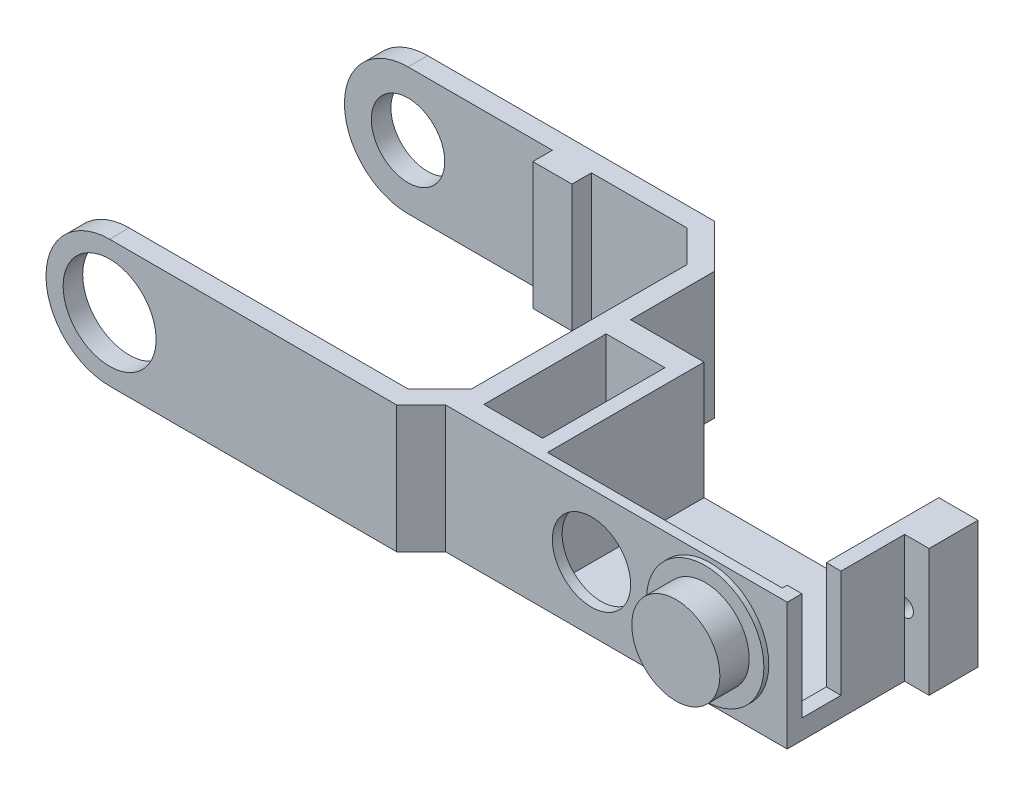
SolidWorks part; units mm, degrees
material "uhlíková ocel 7850"
ref_plane "Přední rovina" through (0, 0, 0) normal (0, 0, 1) x (1, 0, 0)
ref_plane "Horní rovina" through (0, 0, 0) normal (0, 1, 0) x (1, 0, 0)
ref_plane "Pravá rovina" through (0, 0, 0) normal (1, 0, 0) x (0, 0, -1)
sketch "Skica1" plane through (0, 0, 0) normal (0, 1, 0) x (1, 0, 0)
  line L0 (0, -11) -> (0, 11)
  line L1 (0, 11) -> (-3.25, 14.25)
  line L2 (-3.25, 14.25) -> (-38.25, 14.25)
  line L3 (-38.25, 14.25) -> (-38.25, 16.25)
  line L4 (-38.25, 16.25) -> (-2.4216, 16.25)
  line L5 (-2.4216, 16.25) -> (2, 11.8284)
  line L6 (2, 11.8284) -> (2, -11.8284)
  line L7 (2, 0) -> (0, 0) construction
  line L8 (-2.4216, -16.25) -> (2, -11.8284)
  line L9 (-38.25, -16.25) -> (-2.4216, -16.25)
  line L10 (-38.25, -14.25) -> (-38.25, -16.25)
  line L11 (-3.25, -14.25) -> (-38.25, -14.25)
  line L12 (0, -11) -> (-3.25, -14.25)
  dimension "D1" = 11
  dimension "D2" = 135
  dimension "D3" = 35
  dimension "D4" = 2
  dimension "D5" = 2
  dimension "D6" = 2
  dimension "D7" = 14.25
extrude "Přidat vysunutím1" add sketch "Skica1" along normal blind 13
sketch "Skica2" plane through (0, 0, 0) normal (0, -1, 0) x (1, 0, 0)
  line L0 (0.0784, 13.75) -> (35, 13.75)
  line L1 (-2.4216, 16.25) -> (2, 11.8284) construction
  line L2 (35, 13.75) -> (35, 1.75)
  line L3 (35, 1.75) -> (37.5, 1.75)
  line L4 (37.5, 1.75) -> (37.5, -3.25)
  line L5 (37.5, -3.25) -> (2, -3.25)
  line L6 (2, 11.8284) -> (2, -11.8284) construction
  line L7 (2, -3.25) -> (2, 11.8284)
  line L8 (2, 11.8284) -> (0.0784, 13.75)
  line L9 (-38.25, 16.25) -> (-2.4216, 16.25) construction
  line L10 (0, -11) -> (0, 11) construction
  dimension "D1" = 2.5
  dimension "D2" = 35
  dimension "D3" = 12
  dimension "D4" = 5
  dimension "D5" = 2.5
extrude "Přidat vysunutím2" add sketch "Skica2" against normal up to surface (13 mm away) up to face at (-13.3619, 13, 0)
sketch "Skica3" plane through (0, 13, 0) normal (0, 1, 0) x (1, 0, 0)
  line L0 (0, 11) -> (0, -11) construction
  line L1 (2, 0.75) -> (8, 0.75)
  line L2 (2, 0.75) -> (2, -11.75)
  line L3 (2, -11.75) -> (8, -11.75)
  line L4 (8, 0.75) -> (8, -11.75)
  line L5 (37.5, 3.25) -> (2, 3.25) construction
  line L6 (0.0784, -13.75) -> (35, -13.75) construction
  dimension "D1" = 2
  dimension "D2" = 2.5
  dimension "D3" = 2
  dimension "D4" = 6
extrude "Odebrat vysunutím1" cut sketch "Skica3" against normal through all
sketch "Skica4" plane through (0, 13, 0) normal (0, 1, 0) x (1, 0, 0)
  line L0 (37.5, 3.25) -> (2, 3.25) construction
  line L1 (9.5, 3.25) -> (33.5, 3.25)
  line L2 (9.5, 3.25) -> (9.5, -12.75)
  line L3 (9.5, -12.75) -> (33.5, -12.75)
  line L4 (33.5, 3.25) -> (33.5, -12.75)
  line L5 (0.0784, -13.75) -> (35, -13.75) construction
  line L6 (35, -13.75) -> (35, -1.75) construction
  dimension "D1" = 1
  dimension "D2" = 1.5
  dimension "D3" = 24
extrude "Odebrat vysunutím2" cut sketch "Skica4" against normal blind 12
sketch "Skica5" plane through (0, 0, -3.25) normal (0, 0, -1) x (-1, 0, 0)
  circle A0 centre (-34.9938, 6.5551) radius 1.1906 construction
  circle A1 centre (-8.0063, 6.5551) radius 1.1906 construction
  circle A2 centre (-34.9938, 6.5551) radius 0.9
  circle A3 centre (-8.0063, 6.5551) radius 0.9
  dimension "D1" = 1.8
extrude "Odebrat vysunutím3" cut sketch "Skica5" against normal blind 5 contours A1 | A2 | A3 region at (34.9938, 6.5551, -3.25) region at (8.0063, 6.5551, -3.25)
fillet "Zaoblit1" radius 6.5 4 edges at (-38.25, 0, -15.25) (-38.25, 0, 15.25) (-38.25, 13, 15.25) (-38.25, 13, -15.25)
sketch "Skica6" plane through (0, 0, -16.25) normal (0, 0, -1) x (-1, 0, 0)
  circle A0 centre (31.75, 6.5) radius 3.75
  dimension "D1" = 7.5
extrude "Odebrat vysunutím4" cut sketch "Skica6" against normal blind 5
sketch "Skica7" plane through (0, 0, 14.25) normal (0, 0, -1) x (-1, 0, 0)
  circle A0 centre (31.75, 6.5) radius 4.75
  dimension "D1" = 9.5
extrude "Odebrat vysunutím5" cut sketch "Skica7" against normal blind 5
sketch "Skica8" plane through (35, 0, 0) normal (1, 0, 0) x (0, 0, -1)
  line L0 (-13.75, 13) -> (-1.75, 13) construction
  line L1 (-12.25, 13) -> (-8.25, 13)
  line L2 (-12.25, 13) -> (-12.25, 2)
  line L3 (-12.25, 2) -> (-8.25, 2)
  line L4 (-8.25, 13) -> (-8.25, 2)
  line L5 (-13.75, 13) -> (-13.75, 0) construction
  dimension "D1" = 1.5
  dimension "D2" = 4
  dimension "D3" = 11
extrude "Odebrat vysunutím6" cut sketch "Skica8" against normal blind 5
sketch "Skica9" plane through (0, 0, 13.75) normal (0, 0, 1) x (1, 0, 0)
  line L0 (-22.25, 6.555) -> (27.1188, 6.555) construction
  line L3 (35, 13) -> (35, 0) construction
  circle A0 centre (15, 6.555) radius 4
  dimension "D1" = 8
  dimension "D2" = 20
extrude "Odebrat vysunutím7" cut sketch "Skica9" against normal blind 10
sketch "Skica10" plane through (0, 0, 13.75) normal (0, 0, 1) x (1, 0, 0)
  circle A0 centre (27.1188, 6.555) radius 6
  dimension "D1" = 12
extrude "Přidat vysunutím3" add sketch "Skica10" along normal blind 0.5
sketch "Skica11" plane through (0, 0, 14.25) normal (0, 0, 1) x (1, 0, 0)
  circle A0 centre (27.1188, 6.555) radius 4.5
  dimension "D1" = 9
extrude "Přidat vysunutím4" add sketch "Skica11" along normal blind 3
sketch "Skica12" plane through (0, 13, 0) normal (0, 1, 0) x (1, 0, 0)
  line L0 (-31.75, 14.25) -> (-3.25, 14.25) construction
  line L1 (-17, 14.25) -> (-13, 14.25)
  line L2 (-17, 14.25) -> (-17, 12.25)
  line L3 (-17, 12.25) -> (-13, 12.25)
  line L4 (-13, 14.25) -> (-13, 12.25)
  line L5 (0, 11) -> (0, -11) construction
  point P6 (-15, 12.25)
  dimension "D1" = 4
  dimension "D2" = 2
  dimension "D3" = 15
extrude "Přidat vysunutím5" add sketch "Skica12" against normal up to surface (13 mm away) up to face at (5, 0, 5.5)
